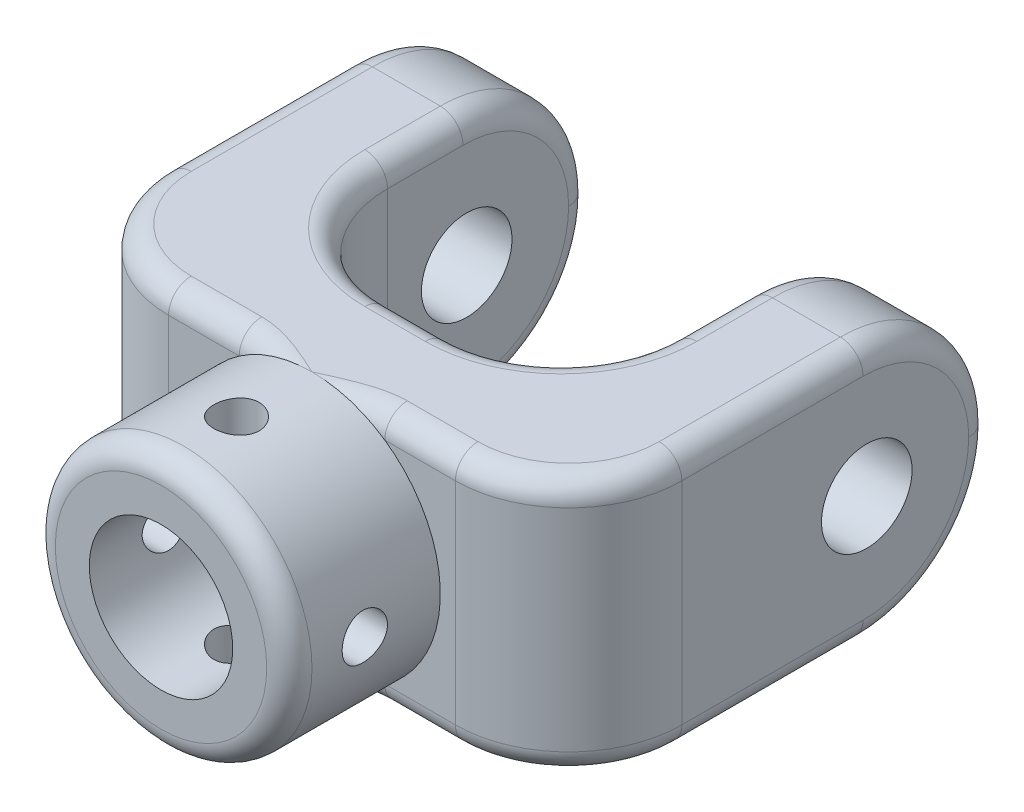
SolidWorks part; units mm, degrees
ref_plane "Front Plane" through (0, 0, 0) normal (0, 0, 1) x (1, 0, 0)
ref_plane "Top Plane" through (0, 0, 0) normal (0, 1, 0) x (1, 0, 0)
ref_plane "Right Plane" through (0, 0, 0) normal (1, 0, 0) x (0, 0, -1)
sketch "Sketch1" plane through (0, 0, 0) normal (0, 1, 0) x (1, 0, 0)
  line L0 (-863.6, 0) -> (863.6, 0)
  line L1 (863.6, 0) -> (863.6, 1422.4)
  line L2 (863.6, 1422.4) -> (482.6, 1422.4)
  line L3 (482.6, 1422.4) -> (482.6, 355.6)
  line L4 (482.6, 355.6) -> (-482.6, 355.6)
  line L5 (0, 355.6) -> (0, 0) construction
  line L6 (-482.6, 1422.4) -> (-482.6, 355.6)
  line L7 (-863.6, 1422.4) -> (-482.6, 1422.4)
  line L8 (-863.6, 0) -> (-863.6, 1422.4)
  dimension "D1" = 863.6
  dimension "D2" = 355.6
  dimension "D3" = 482.6
  dimension "D4" = 1422.4
extrude "Boss-Extrude1" add sketch "Sketch1" along normal mid plane 863.6
fillet "Fillet1" radius 431.8 4 edges at (-673.1, -431.8, -1422.4) (-673.1, 431.8, -1422.4) (673.1, -431.8, -1422.4) (673.1, 431.8, -1422.4)
sketch "Sketch2" plane through (0, 0, 0) normal (0, 0, 1) x (1, 0, 0)
  circle A0 centre (0, 0) radius 431.8
  dimension "D1" = 863.6
extrude "Boss-Extrude2" add sketch "Sketch2" along normal blind 508
fillet "Fillet2" radius 76.2 1 edges at (431.8, 0, 508)
fillet "Fillet3" radius 381 4 edges at (-482.6, 0, -355.6) (482.6, 0, -355.6) (863.6, 0, 0) (-863.6, 0, 0)
fillet "Fillet4" radius 76.2 30 edges at (-863.6, 305.3287, -1295.9287) (-863.6, -305.3287, -1295.9287) (-863.6, -431.8, -685.8) (-752.0077, -431.8, -111.5923) (-241.3, -431.8, 0) (241.3, -431.8, 0) (752.0077, -431.8, -111.5923) (863.6, -431.8, -685.8) (863.6, -305.3287, -1295.9287) (863.6, 305.3287, -1295.9287) (863.6, 431.8, -685.8) (752.0077, 431.8, -111.5923) (241.3, 431.8, 0) (-241.3, 431.8, 0) (-752.0077, 431.8, -111.5923) (-863.6, 431.8, -685.8) (-371.0077, 431.8, -467.1923) (0, 431.8, -355.6) (371.0077, 431.8, -467.1923) (482.6, 431.8, -863.6) (482.6, 305.3287, -1295.9287) (482.6, -305.3287, -1295.9287) (482.6, -431.8, -863.6) (371.0077, -431.8, -467.1923) (0, -431.8, -355.6) (-371.0077, -431.8, -467.1923) (-482.6, -431.8, -863.6) (-482.6, -305.3287, -1295.9287) (-482.6, 305.3287, -1295.9287) (-482.6, 431.8, -863.6)
sketch "Sketch3" plane through (0, 0, 508) normal (0, 0, 1) x (1, 0, 0)
  circle A0 centre (0, 0) radius 241.3
  dimension "D1" = 482.6
extrude "Cut-Extrude1" cut sketch "Sketch3" against normal through all
sketch "Sketch4" plane through (863.6, 0, 0) normal (1, 0, 0) x (0, 0, -1)
  circle A0 centre (1003.3, 0) radius 152.4
  dimension "D1" = 304.8
  dimension "D2" = 342.9
extrude "Cut-Extrude2" cut sketch "Sketch4" against normal through all
sketch "Sketch5" plane through (0, 0, 0) normal (0, 1, 0) x (1, 0, 0)
  line L0 (-355.6, -508) -> (355.6, -508) construction
  circle A0 centre (0, -254) radius 76.2
  point P5 (0, 0)
  dimension "D1" = 152.4
  dimension "D2" = 254
extrude "Cut-Extrude3" cut sketch "Sketch5" against normal through all
pattern_circular "CirPattern1" count 4 every 90 about axis through (0, 0, 508) along (0, 0, -1) of "Cut-Extrude3"
